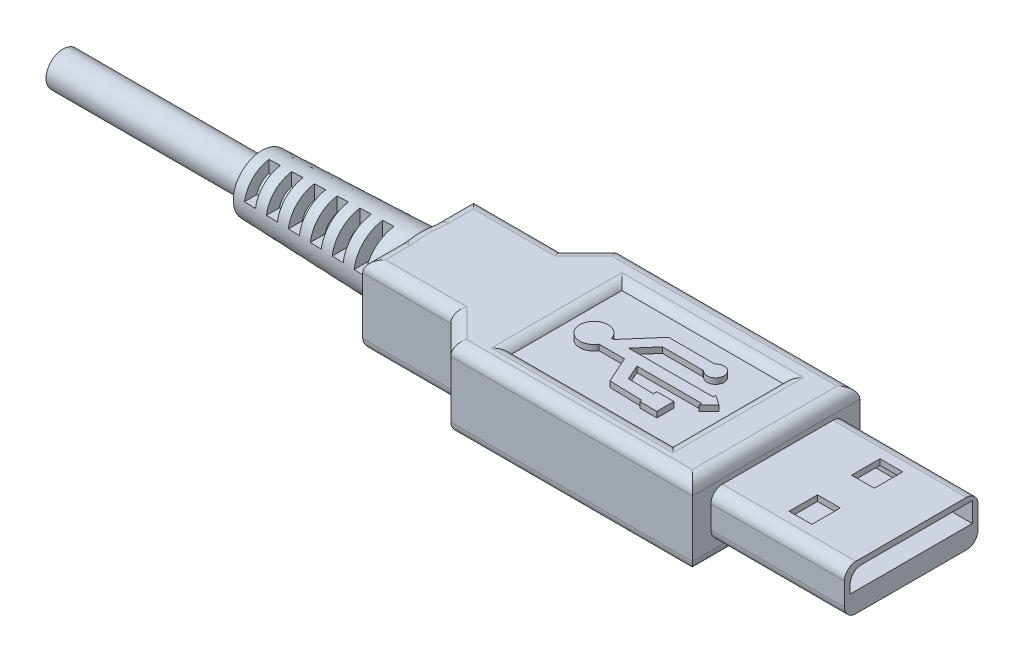
SolidWorks part; units mm, degrees
ref_plane "Alzado" through (0, 0, 0) normal (0, 0, 1) x (1, 0, 0)
ref_plane "Planta" through (0, 0, 0) normal (0, 1, 0) x (1, 0, 0)
ref_plane "Vista lateral" through (0, 0, 0) normal (1, 0, 0) x (0, 0, -1)
sketch "Croquis1" plane through (0, 0, 0) normal (0, 1, 0) x (1, 0, 0)
  line L0 (0, 29.5) -> (126, 29.5) construction
  line L1 (41, 0) -> (126, 0)
  line L2 (0, 10) -> (0, 49)
  line L3 (41, 59) -> (126, 59)
  line L4 (126, 0) -> (126, 59)
  line L5 (0, 49) -> (31, 49)
  line L6 (0, 10) -> (31, 10)
  line L7 (31, 49) -> (41, 59)
  line L8 (31, 10) -> (41, 0)
  dimension "D2" = 59
  dimension "D3" = 135
  dimension "D4" = 31
  dimension "D5" = 10
extrude "Saliente-Extruir1" add sketch "Croquis1" along normal blind 28
sketch "Croquis2" plane through (0, 0, 0) normal (-1, 0, 0) x (0, 0, 1)
  line L0 (-49, 0) -> (-10, 28) construction
  circle A0 centre (-29.5, 14) radius 12
  dimension "D1" = 24
extrude "Saliente-Extruir2" add sketch "Croquis2" along normal blind 55 draft 2
sketch "Croquis3" plane through (-55, 0, 0) normal (-1, 0, 0) x (0, 0, 1)
  circle A0 centre (-29.5, 14) radius 6
  dimension "D1" = 12
extrude "Saliente-Extruir3" add sketch "Croquis3" along normal blind 70
sketch "Croquis4" plane through (0, 28, 0) normal (0, 1, 0) x (1, 0, 0)
  line L0 (126, 48.223) -> (126, 30.3185) construction
  line L1 (53, 9.223) -> (110, 9.223)
  line L2 (53, 9.223) -> (53, 48.223)
  line L3 (53, 48.223) -> (110, 48.223)
  line L4 (110, 9.223) -> (110, 48.223)
  line L5 (126, 0) -> (126, 59) construction
  line L6 (126, 30.3185) -> (30.3186, 30.3185) construction
  dimension "D1" = 57
  dimension "D2" = 39
  dimension "D3" = 16
extrude "Cortar-Extruir1" cut sketch "Croquis4" against normal blind 2
sketch "Croquis7" plane through (0, 26, 0) normal (0, 1, 0) x (1, 0, 0)
  line L0 (53, 38.223) -> (109.6815, 38.223) construction
  line L2 (53, 48.223) -> (53, 9.223) construction
  line L3 (53, 28.3861) -> (109.6815, 28.3861) construction
  line L6 (53, 48.223) -> (53, 9.223) construction
  line L7 (110, 48.223) -> (53, 48.223) construction
  line L8 (53, 18.5492) -> (109.6815, 18.5492) construction
  line L9 (103.471, 30.8571) -> (103.471, 24.8571)
  line L14 (92, 21.5492) -> (98, 21.5492)
  line L15 (92, 21.5492) -> (92, 15.5492)
  line L16 (92, 15.5492) -> (98, 15.5492)
  line L17 (98, 21.5492) -> (98, 15.5492)
  line L18 (92, 21.5492) -> (98, 15.5492) construction
  line L19 (92, 15.5492) -> (98, 21.5492) construction
  line L20 (103.471, 24.8571) -> (107, 28.3861)
  line L21 (103.471, 30.8571) -> (107, 28.3861)
  line L22 (110, 9.223) -> (110, 48.223) construction
  line L23 (110, 9.223) -> (110, 48.223) construction
  circle A0 centre (63, 28.3861) radius 5
  circle A1 centre (96, 38.223) radius 3
  point P16 (95, 18.5492)
  dimension "D2" = 10
  dimension "D4" = 6
  dimension "D1" = 10
  dimension "D3" = 10
  dimension "D5" = 33
  dimension "D6" = 6
  dimension "D7" = 6
  dimension "D8" = 15
  dimension "D9" = 6
  dimension "D10" = 3
  dimension "D11" = 80
extrude "Saliente-Extruir4" add sketch "Croquis7" along normal blind 2
sketch "Croquis8" plane through (0, 26, 0) normal (0, 1, 0) x (1, 0, 0)
  line L0 (103.471, 27.8571) -> (64.0668, 27.8571) construction
  line L1 (93.6667, 38.1943) -> (78.3945, 38.1943) construction
  line L2 (78.3945, 38.1943) -> (69.3857, 27.8571) construction
  line L3 (103.471, 30.8571) -> (103.471, 24.8571) construction
  line L4 (92.5942, 18.2461) -> (81.7407, 18.5464) construction
  line L5 (81.7407, 18.5464) -> (77.5794, 27.8571) construction
  line L6 (92.6495, 20.2453) -> (83.0534, 20.5109)
  line L7 (83.0534, 20.5109) -> (80.664, 25.8571)
  line L8 (93.6667, 40.1943) -> (77.4846, 40.1943)
  line L9 (77.4846, 40.1943) -> (68.4757, 29.8571)
  line L10 (103.471, 29.8571) -> (73.7816, 29.8571)
  line L11 (92.5389, 16.2469) -> (80.428, 16.582)
  line L12 (80.428, 16.582) -> (76.2826, 25.8571)
  line L13 (93.6667, 36.1943) -> (79.3045, 36.1943)
  line L14 (79.3045, 36.1943) -> (73.7816, 29.8571)
  line L15 (103.471, 25.8571) -> (80.664, 25.8571)
  line L16 (64.0668, 29.8571) -> (64.0668, 25.8571)
  line L17 (93.6667, 40.1943) -> (93.6667, 36.1943)
  line L18 (92.6495, 20.2453) -> (92.5389, 16.2469)
  line L19 (76.2826, 25.8571) -> (64.0668, 25.8571)
  line L20 (77.4846, 40.1943) -> (67.8779, 29.1711) construction
  line L21 (79.3045, 36.1943) -> (70.8934, 26.5431) construction
  line L22 (80.428, 16.582) -> (75.7535, 27.041) construction
  line L23 (68.4757, 29.8571) -> (64.0668, 29.8571)
  line L24 (83.0534, 20.5109) -> (79.4054, 28.6732) construction
  line L25 (103.471, 25.8571) -> (64.0668, 25.8571) construction
  line L26 (103.471, 29.8571) -> (103.471, 25.8571)
  line L27 (103.471, 29.8571) -> (64.0668, 29.8571) construction
  dimension "D1" = 2
  dimension "D2" = 2
extrude "Saliente-Extruir5" add sketch "Croquis8" along normal blind 2
sketch "Croquis9" plane through (126, 0, 0) normal (1, 0, 0) x (0, 0, -1)
  line L0 (0, 0) -> (59, 28) construction
  line L1 (51.589, 20.2795) -> (8.589, 20.2795)
  line L2 (53.589, 22.2795) -> (6.589, 22.2795)
  line L3 (53.589, 22.2795) -> (53.589, 6.2795)
  line L4 (53.589, 6.2795) -> (6.589, 6.2795)
  line L5 (6.589, 22.2795) -> (6.589, 6.2795)
  line L6 (53.589, 22.2795) -> (6.589, 6.2795) construction
  line L7 (53.589, 6.2795) -> (6.589, 22.2795) construction
  line L8 (8.589, 20.2795) -> (8.589, 8.2795)
  line L9 (51.589, 8.2795) -> (8.589, 8.2795)
  line L10 (51.589, 20.2795) -> (51.589, 8.2795)
  point P4 (30.089, 14.2795)
  dimension "D1" = 47
  dimension "D2" = 16
  dimension "D3" = 2
extrude "Saliente-Extruir6" add sketch "Croquis9" along normal blind 47
sketch "Croquis11" plane through (0, 22.2795, 0) normal (0, 1, 0) x (1, 0, 0)
  line L0 (173, 30.089) -> (126, 30.089) construction
  line L1 (173, 53.589) -> (173, 6.589) construction
  line L2 (126, 53.589) -> (126, 6.589) construction
  line L4 (146, 46.089) -> (154, 46.089)
  line L5 (146, 46.089) -> (146, 36.089)
  line L6 (146, 36.089) -> (154, 36.089)
  line L7 (154, 46.089) -> (154, 36.089)
  line L8 (146, 46.089) -> (154, 36.089) construction
  line L9 (146, 36.089) -> (154, 46.089) construction
  line L10 (126, 0) -> (126, 59) construction
  line L11 (146, 24.089) -> (154, 24.089)
  line L12 (154, 14.089) -> (154, 24.089)
  line L13 (146, 14.089) -> (154, 14.089)
  line L14 (146, 14.089) -> (146, 24.089)
  point P6 (150, 41.089)
  dimension "D1" = 11
  dimension "D2" = 24
  dimension "D3" = 8
  dimension "D4" = 10
extrude "Cortar-Extruir2" cut sketch "Croquis11" against normal through all
sketch "Croquis12" plane through (173, 0, 0) normal (1, 0, 0) x (0, 0, -1)
  line L0 (51.589, 8.2795) -> (51.589, 20.2795) construction
  line L1 (8.589, 8.2795) -> (51.589, 8.2795)
  line L2 (8.589, 8.2795) -> (8.589, 13.2795)
  line L3 (8.589, 13.2795) -> (51.589, 13.2795)
  line L4 (51.589, 8.2795) -> (51.589, 13.2795)
  point P7 (8.589, 10.7795)
  dimension "D1" = 2.5
extrude "Saliente-Extruir8" add sketch "Croquis12" against normal up to surface (47 mm away) up to face at (126, 14, -29.5)
fillet "Redondeo1" radius 4 20 edges at (83.5, 0, -59) (36, 0, -54) (15.5, 0, -49) (0, 0, -29.5) (15.5, 0, -10) (36, 0, -5) (83.5, 0, 0) (126, 0, -29.5) (83.5, 28, 0) (36, 28, -5) (15.5, 28, -10) (0, 28, -29.5) (15.5, 28, -49) (36, 28, -54) (83.5, 28, -59) (126, 28, -29.5) (110, 28, -28.723) (81.5, 28, -48.223) (53, 28, -28.723) (81.5, 28, -9.223)
fillet "Redondeo3" radius 4 4 edges at (149.5, 6.2795, -53.589) (149.5, 6.2795, -6.589) (149.5, 22.2795, -53.589) (149.5, 20.2795, -8.589)
fillet "Redondeo4" radius 4 1 edges at (149.5, 22.2795, -6.589)
sketch "Croquis13" plane through (-55, 0, 0) normal (-1, 0, 0) x (0, 0, 1)
  line L0 (-29.5, 30.5587) -> (-29.5, 14) construction
  line L1 (-29.5, 14) -> (-3.6697, 14) construction
  line L2 (-13.3956, 30.5587) -> (-13.3956, 15.5)
  line L8 (-28, 19.8095) -> (-28, 30.5587)
  line L9 (-28, 30.5587) -> (-13.3956, 30.5587)
  line L11 (-13.3956, 15.5) -> (-23.6905, 15.5)
  arc A0 (-23.6905, 15.5) -> (-28, 19.8095) centre (-29.5, 14) ccw
  circle A1 centre (-29.5, 14) radius 6
  arc A2 (-29.5, 20) -> (-23.5, 14) centre (-29.5, 14) ccw
  dimension "D2" = 1.5
  dimension "D3" = 1.5
  dimension "D1" = 0
extrude "Cortar-Extruir3" cut sketch "Croquis13" against normal blind 4 from offset 4 contours A0 L8 L9 L2 L11 offset against normal yes
pattern_linear "MatrizL1" count 6 spacing 8 along (1, 0, 0) of "Cortar-Extruir3"
pattern_circular "MatrizC1" count 3 over 360 about axis through (-125, 14, -29.5) along (1, 0, 0) of "MatrizL1" reverse direction yes
